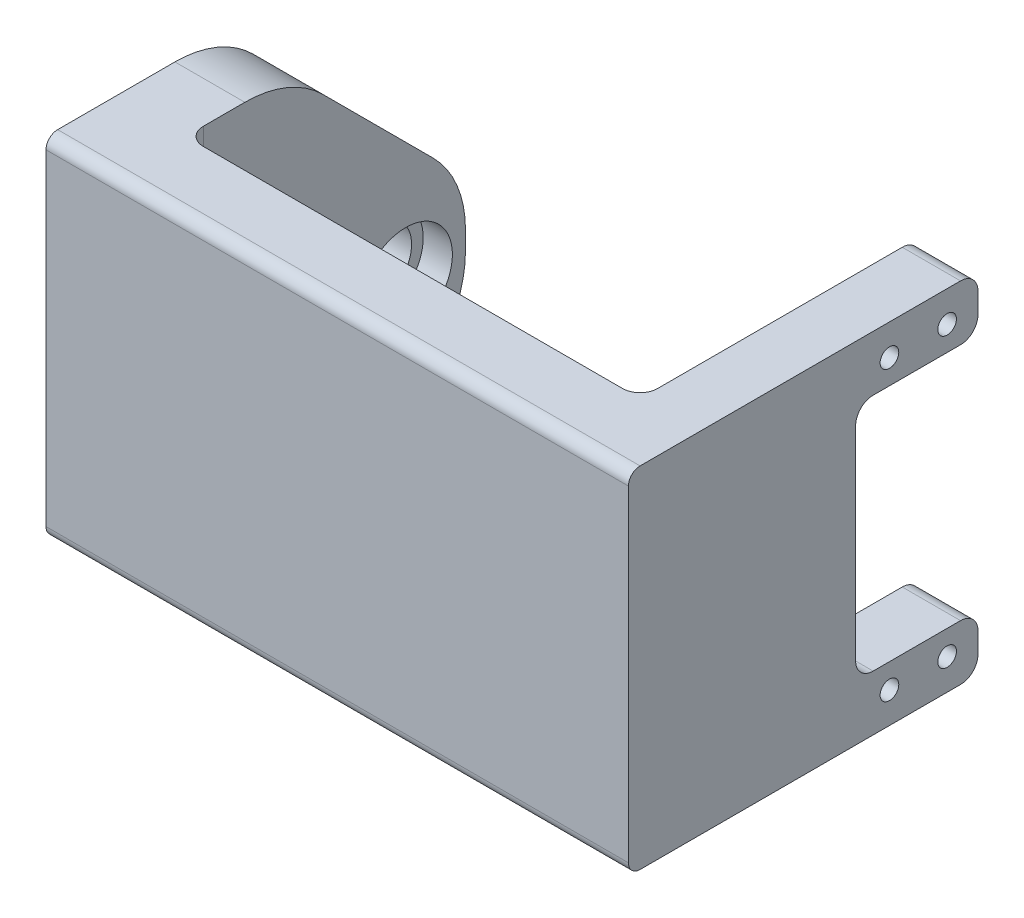
SolidWorks part; units mm, degrees
ref_plane "Front Plane" through (0, 0, 0) normal (0, 0, 1) x (1, 0, 0)
ref_plane "Top Plane" through (0, 0, 0) normal (0, 1, 0) x (1, 0, 0)
ref_plane "Right Plane" through (0, 0, 0) normal (1, 0, 0) x (0, 0, -1)
sketch "Sketch1" plane through (0, 0, 0) normal (0, 1, 0) x (1, 0, 0)
  line L0 (0, 0) -> (0, 60)
  line L1 (0, 60) -> (12, 60)
  line L2 (12, 60) -> (12, 12)
  line L3 (12, 12) -> (89.97, 12)
  line L4 (89.97, 12) -> (89.97, 60)
  line L5 (89.97, 60) -> (99.97, 60)
  line L6 (99.97, 60) -> (99.97, 0)
  line L7 (99.97, 0) -> (0, 0)
  dimension "D1" = 12
  dimension "D2" = 48
  dimension "D3" = 10
  dimension "D4" = 77.97
  dimension "D5" = 60
extrude "Boss-Extrude1" add sketch "Sketch1" along normal blind 60
sketch "Sketch2" plane through (99.97, 0, 0) normal (1, 0, 0) x (0, 0, -1)
  line L0 (44.8, 5.305) -> (44.8, 54.695) construction
  line L1 (0, 30) -> (44.8, 30) construction
  line L2 (0, 60) -> (0, 0) construction
  line L3 (9.9, 30) -> (54.7, 30) construction
  line L4 (60, 60) -> (60, 0) construction
  line L5 (49.75, 54.695) -> (49.75, 19.58) construction
  line L6 (44.8, 54.695) -> (54.7, 54.695) construction
  circle A0 centre (44.8, 54.695) radius 1.6
  circle A1 centre (44.8, 5.305) radius 1.6
  circle A2 centre (54.7, 54.695) radius 1.6
  circle A3 centre (54.7, 5.305) radius 1.6
  circle A4 centre (49.75, 19.58) radius 8
  circle A5 centre (49.75, 19.58) radius 6
  dimension "D2" = 3.2
  dimension "D5" = 5.3
  dimension "D7" = 16
  dimension "D1" = 49.39
  dimension "D4" = 9.9
  dimension "D6" = 14.275
  dimension "D8" = 2
  dimension "D3" = 2
extrude "Cut-Extrude1" cut sketch "Sketch2" against normal up to next contours A0 | A2 | A3 | A1 region at (99.97, 54.695, -44.8) region at (99.97, 5.305, -44.8) region at (99.97, 54.695, -54.7) region at (99.97, 5.305, -54.7)
sketch "Sketch3" plane through (99.97, 0, 0) normal (1, 0, 0) x (0, 0, -1)
  line L0 (60, 60) -> (60, 0) construction
  line L1 (60, 50.5) -> (39, 50.5)
  line L2 (60, 50.5) -> (60, 9.5)
  line L3 (60, 9.5) -> (39, 9.5)
  line L4 (39, 50.5) -> (39, 9.5)
  point P8 (60, 30)
  dimension "D1" = 41
  dimension "D2" = 21
extrude "Cut-Extrude2" cut sketch "Sketch3" against normal up to next
extrude "Cut-Extrude3" cut sketch "Sketch2<3>" against normal blind 5 from surface contours A4 A5 | A5 region at (99.97, 19.58, -41.9763) region at (99.97, 19.58, -49.75) starting at face at (12, 30, -36)
sketch "Sketch2<3>" plane through (99.97, 0, 0) normal (1, 0, 0) x (0, 0, -1) same geometry as "Sketch2"
extrude "Cut-Extrude4" cut sketch "Sketch2<4>" against normal through all from surface contours A5 region at (99.97, 19.58, -49.75) starting at face at (7, 19.58, -41.75)
sketch "Sketch2<4>" plane through (99.97, 0, 0) normal (1, 0, 0) x (0, 0, -1) same geometry as "Sketch2"
chamfer "Chamfer1" distance 30 angle 45 1 edges at (6, 60, -60)
fillet "Fillet1" radius 19 3 edges at (6, 0, -60) (6, 60, -30) (6, 30, -60)
fillet "Fillet2" radius 3 8 edges at (12, 30, -12) (89.97, 30, -12) (94.97, 50.5, -39) (94.97, 9.5, -39) (94.97, 0, -60) (94.97, 9.5, -60) (94.97, 50.5, -60) (94.97, 60, -60)
fillet "Fillet3" radius 2 2 edges at (49.985, 0, 0) (49.985, 60, 0)
move or copy body "Body-Move/Copy1" [suppressed] bodies to move or copy 106
